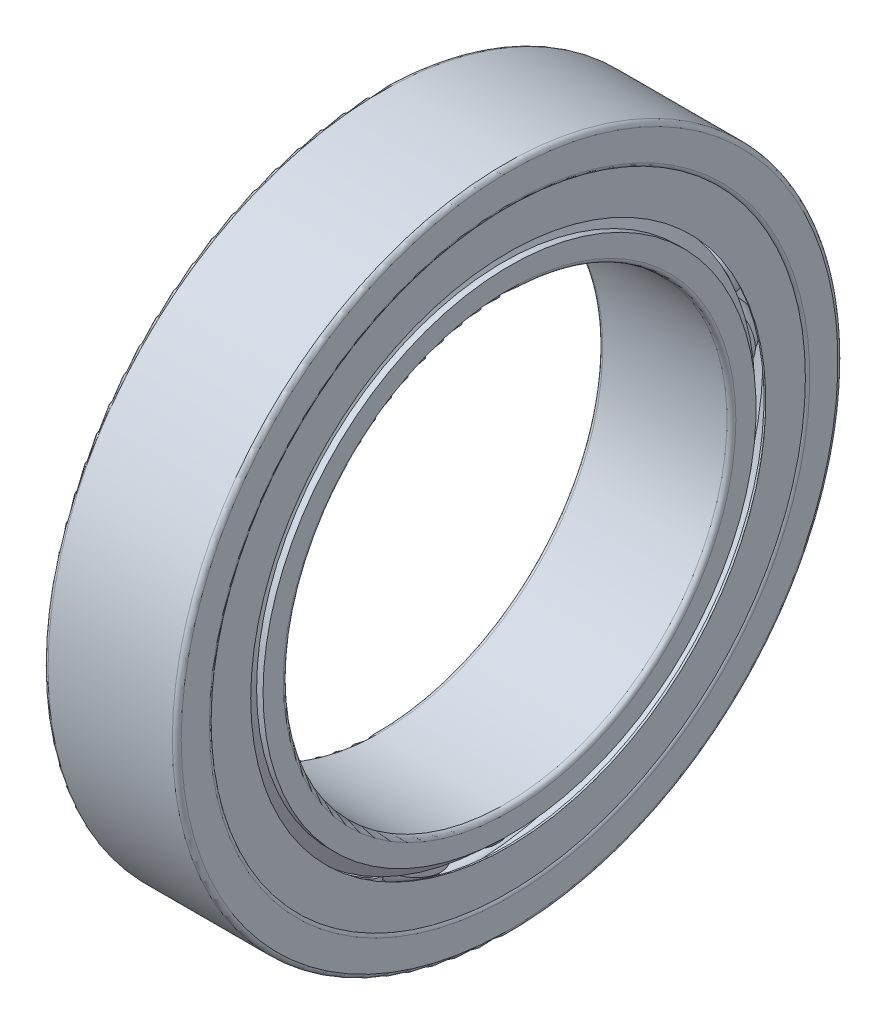
SolidWorks part; units mm, degrees
ref_plane "前视基准面" through (0, 0, 0) normal (0, 0, 1) x (1, 0, 0)
ref_plane "上视基准面" through (0, 0, 0) normal (0, 1, 0) x (1, 0, 0)
ref_plane "右视基准面" through (0, 0, 0) normal (1, 0, 0) x (0, 0, -1)
sketch "尺寸草图" plane through (0, 0, 0) normal (0, 0, 1) x (1, 0, 0)
  line L0 (-19.9271, 0) -> (19.9271, 0) construction
  line L1 (0, 21.603) -> (0, -21.603) construction
  line L2 (-1.4, 7.5) -> (1.4, 7.5)
  line L3 (1.5, 7.4) -> (1.5, 6.7667)
  line L4 (-1.5, 7.4) -> (-1.5, 6.7667)
  line L5 (-1.4, 6.6667) -> (1.4, 6.6667)
  line L6 (-3.5, 6.25) -> (3.3577, 6.25) construction
  line L7 (-1.4, 5.8333) -> (1.4, 5.8333)
  line L8 (1.5, 5.7333) -> (1.5, 5.1)
  line L9 (1.4, 5) -> (-1.4, 5)
  line L10 (-1.5, 5.1) -> (-1.5, 5.7333)
  line L11 (0, 6.25) -> (0, 6.875) construction
  line L13 (1.4, 6.6667) -> (1.4, 5.8333)
  line L14 (1.1944, 5.8333) -> (1.3548, 5.5556)
  line L15 (1.3548, 5.5556) -> (1.5, 5.5556)
  line L16 (1.4707, 6.696) -> (1.4707, 5.804)
  circle A0 centre (0, 6.25) radius 0.625
  arc A1 (1.5, 6.7667) -> (1.4, 6.6667) centre (1.4, 6.7667) cw
  arc A2 (1.5, 5.7333) -> (1.4, 5.8333) centre (1.4, 5.7333) ccw
  arc A3 (-1.4, 5.8333) -> (-1.5, 5.7333) centre (-1.4, 5.7333) ccw
  arc A4 (-1.4, 6.6667) -> (-1.5, 6.7667) centre (-1.4, 6.7667) cw
  arc A5 (-1.4, 5) -> (-1.5, 5.1) centre (-1.4, 5.1) cw
  arc A6 (1.4, 5) -> (1.5, 5.1) centre (1.4, 5.1) ccw
  arc A7 (1.5, 7.4) -> (1.4, 7.5) centre (1.4, 7.4) ccw
  arc A8 (-1.4, 7.5) -> (-1.5, 7.4) centre (-1.4, 7.4) ccw
  point P7 (0, 0)
  point P25 (-1.5, 5.8333)
  point P28 (-1.5, 6.6667)
  point P31 (-1.5, 5)
  point P36 (1.5, 7.5)
  point P39 (-1.5, 7.5)
  dimension "D1" = 0.2083
  dimension "D3" = 0.1
  dimension "B" = 3
  dimension "D2" = 1.5
  dimension "D" = 15
  dimension "(d)" = 10
  dimension "D5" = 6.25
  dimension "D6" = 0.8333
  dimension "D7" = 0.8333
  dimension "D8" = 0.2778
  dimension "D9" = 60
  dimension "D10" = 0.3056
sketch "草图2" plane through (0, 0, 0) normal (0, 0, 1) x (1, 0, 0)
  line L0 (1.1944, 5.8333) -> (1.3548, 5.5556) construction
  line L1 (1.3548, 5.5556) -> (1.5, 5.5556) construction
  line L2 (1.1944, 5.8333) -> (1.3548, 5.5556)
  line L3 (1.3548, 5.5556) -> (1.5, 5.5556)
  line L4 (0, 6.875) -> (0, 5.625) construction
  line L5 (-1.3548, 5.5556) -> (-1.5, 5.5556)
  line L6 (1.4, 5) -> (-1.4, 5) construction
  line L7 (-1.1944, 5.8333) -> (-1.3548, 5.5556)
  line L8 (-1.5, 7.4) -> (-1.5, 6.7667) construction
  line L9 (-1.4, 6.6667) -> (1.4, 6.6667) construction
  line L10 (-1.4, 7.5) -> (1.4, 7.5) construction
  line L11 (1.5, 7.4) -> (1.5, 6.7667) construction
  line L12 (1.5, 5.7333) -> (1.5, 5.1) construction
  line L13 (-1.4, 5.8333) -> (1.4, 5.8333) construction
  line L14 (1.4, 5) -> (-1.4, 5)
  line L15 (-1.5, 5.1) -> (-1.5, 5.7333) construction
  line L18 (-3.5, 0) -> (3.5, 0) construction
  line L19 (-19.9271, 0) -> (19.9271, 0) construction
  line L20 (-1.5, 7.4) -> (-1.5, 6.7667)
  line L21 (-1.4, 6.6667) -> (-0.4658, 6.6667)
  line L22 (-1.4, 7.5) -> (1.4, 7.5)
  line L23 (1.5, 7.4) -> (1.5, 6.7667)
  line L24 (1.5, 5.5556) -> (1.5, 5.1)
  line L25 (-1.1944, 5.8333) -> (-0.4658, 5.8333)
  line L26 (-1.5, 5.1) -> (-1.5, 5.5556)
  line L27 (0.4658, 6.6667) -> (1.4, 6.6667)
  line L28 (0.4658, 5.8333) -> (1.1944, 5.8333)
  circle A0 centre (0, 6.25) radius 0.625 construction
  arc A1 (0.4658, 6.6667) -> (-0.4658, 6.6667) centre (0, 6.25) ccw
  arc A2 (-0.4658, 5.8333) -> (0.4658, 5.8333) centre (0, 6.25) ccw
  arc A3 (-1.4, 7.5) -> (-1.5, 7.4) centre (-1.4, 7.4) ccw construction
  arc A4 (-1.5, 6.7667) -> (-1.4, 6.6667) centre (-1.4, 6.7667) ccw construction
  arc A5 (1.5, 7.4) -> (1.4, 7.5) centre (1.4, 7.4) ccw construction
  arc A6 (1.4, 6.6667) -> (1.5, 6.7667) centre (1.4, 6.7667) ccw construction
  arc A8 (1.4, 5) -> (1.5, 5.1) centre (1.4, 5.1) ccw construction
  arc A10 (-1.5, 5.1) -> (-1.4, 5) centre (-1.4, 5.1) ccw construction
  arc A11 (-1.4, 7.5) -> (-1.5, 7.4) centre (-1.4, 7.4) ccw
  arc A12 (-1.5, 6.7667) -> (-1.4, 6.6667) centre (-1.4, 6.7667) ccw
  arc A13 (1.5, 7.4) -> (1.4, 7.5) centre (1.4, 7.4) ccw
  arc A14 (1.4, 6.6667) -> (1.5, 6.7667) centre (1.4, 6.7667) ccw
  arc A16 (1.4, 5) -> (1.5, 5.1) centre (1.4, 5.1) ccw
  arc A18 (-1.5, 5.1) -> (-1.4, 5) centre (-1.4, 5.1) ccw
revolve "旋转1" add sketch "草图2" angle 360 about L18
sketch "草图5" plane through (0, 0, 0) normal (0, 0, 1) x (1, 0, 0)
  line L1 (-0.1875, 6.125) -> (0.1875, 6.125)
  line L2 (-0.1875, 6.125) -> (-0.1875, 6.375)
  line L3 (-0.1875, 6.375) -> (0.1875, 6.375)
  line L4 (0.1875, 6.125) -> (0.1875, 6.375)
  line L5 (-0.1875, 6.125) -> (0.1875, 6.375) construction
  line L6 (-0.1875, 6.375) -> (0.1875, 6.125) construction
  circle A0 centre (0, 6.25) radius 0.625 construction
  circle A1 centre (0, 6.25) radius 0.625 construction
  point P0 (0, 6.25)
  dimension "D3" = 1.25
  dimension "D1" = 0.375
  dimension "D2" = 0.25
revolve "旋转3" add sketch "草图5" angle 360 about L0
sketch "草图3" plane through (0, 0, 0) normal (0, 0, 1) x (1, 0, 0)
  line L1 (-0.6875, 6.25) -> (0.6875, 6.25)
  circle A0 centre (0, 6.25) radius 0.625 construction
  circle A1 centre (0, 6.25) radius 0.625 construction
  arc A2 (0.6875, 6.25) -> (-0.6875, 6.25) centre (0, 6.25) ccw
  dimension "D2" = 1.375
revolve "旋转2" add sketch "草图3" angle 360 about L1 region at (0, 6.5418, 0)
ref_axis "基准轴1" through (-3.85, 0, 0) along (1, 0, 0)
pattern_circular "阵列(圆周)5" count 25 over 360 about axis through (-3.85, 0, 0) along (1, 0, 0) of bodies 103
sketch "草图6" plane through (0, 0, 0) normal (0, 0, 1) x (1, 0, 0)
  line L0 (-0.676, 6.375) -> (0.676, 6.375)
  line L1 (-3.5, 6.25) -> (1.5, 6.25) construction
  line L3 (-0.676, 6.125) -> (0.676, 6.125)
  line L4 (1.5, -7.4) -> (1.5, 7.4) construction
  arc A0 (-0.676, 6.125) -> (0.676, 6.125) centre (0, 6.25) ccw
  circle A1 centre (0, 6.25) radius 0.625 construction
  circle A2 centre (0, 6.25) radius 0.625 construction
  arc A3 (0.676, 6.375) -> (-0.676, 6.375) centre (0, 6.25) ccw
  dimension "D1" = 1.375
  dimension "D2" = 1.25
  dimension "D3" = 0.125
  dimension "D4" = 0.125
revolve "切除-旋转1" cut sketch "草图6" angle 360 about L0
sketch "草图7" plane through (0, 0, 0) normal (0, 0, 1) x (1, 0, 0)
  line L0 (-0.625, 6.25) -> (0.625, 6.25)
  line L1 (-1.5, 0) -> (2.4587, 0) construction
  line L2 (-1.5, 7.4) -> (-1.5, -7.4) construction
  line L3 (-19.9271, 0) -> (19.9271, 0) construction
  circle A0 centre (0, 6.25) radius 0.625 construction
  arc A1 (0.625, 6.25) -> (-0.625, 6.25) centre (0, 6.25) ccw
revolve "旋转4" add sketch "草图7" angle 360 about L0
pattern_circular "阵列(圆周)2" count 25 over 360 about axis through (-3.85, 0, 0) along (1, 0, 0) of "旋转4" reverse direction yes
sketch "草图9" plane through (0, 0, 0) normal (0, 0, 1) x (1, 0, 0)
  line L1 (1.4, 6.6667) -> (1.4, 5.8333) construction
  line L4 (1.4707, 6.696) -> (1.4707, 5.804) construction
  line L5 (1.4, 6.6667) -> (1.4, 5.8333)
  line L6 (1.4707, 6.696) -> (1.4707, 5.804)
  line L7 (-1.4707, 6.696) -> (-1.4707, 5.804)
  line L8 (0, 7.5) -> (0, 0) construction
  line L9 (-1.4, 7.5) -> (1.4, 7.5) construction
  line L10 (-1.4, 6.6667) -> (-1.4, 5.8333)
  arc A0 (1.4, 6.6667) -> (1.5, 6.7667) centre (1.4, 6.7667) ccw construction
  arc A1 (1.4, 6.6667) -> (1.4707, 6.696) centre (1.4, 6.7667) ccw
  arc A2 (1.5, 5.7333) -> (1.4, 5.8333) centre (1.4, 5.7333) ccw construction
  arc A3 (1.4707, 5.804) -> (1.4, 5.8333) centre (1.4, 5.7333) ccw
  arc A4 (-1.4707, 5.804) -> (-1.4, 5.8333) centre (-1.4, 5.7333) cw
  arc A5 (-1.4, 6.6667) -> (-1.4707, 6.696) centre (-1.4, 6.7667) cw
revolve "旋转5" add sketch "草图9" angle 360 about L0
